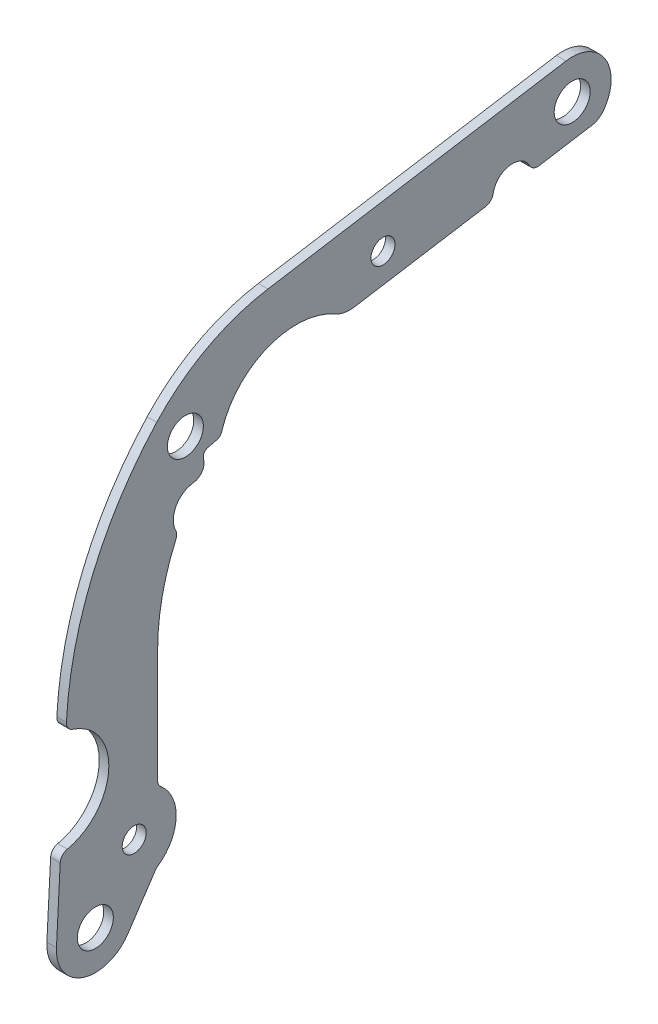
SolidWorks part; units mm, degrees
ref_plane "Front Plane" through (0, 0, 0) normal (0, 0, 1) x (1, 0, 0)
ref_plane "Top Plane" through (0, 0, 0) normal (0, 1, 0) x (1, 0, 0)
ref_plane "Right Plane" through (0, 0, 0) normal (1, 0, 0) x (0, 0, -1)
sketch "Sketch4" plane through (0, 0, 0) normal (1, 0, 0) x (0, 0, -1)
  line L1 (48.6487, 138.1253) -> (75.575, 142.4975) construction
  line L3 (57.5617, 155.7821) -> (157.0154, 171.931)
  line L4 (86.5165, 136.1694) -> (165.6977, 149.0264)
  line L5 (-12.9822, 0.6804) -> (-11.7283, 24.6061)
  line L6 (20.7807, 30.6129) -> (20.7807, 69.93)
  line L7 (20.7807, 30.6129) -> (20.3705, 7.1165) construction
  line L8 (10.8159, -7.2122) -> (20.3705, 7.1165)
  line L9 (0, 0) -> (159.099, 159.099) construction
  line L10 (0, 0) -> (0, 169.8564) construction
  line L11 (-10.2334, 53.1304) -> (-8.2428, 91.114) construction
  line L12 (20.4622, 135.7972) -> (39.6003, 118.1979) construction
  arc A0 (79.9562, 137.3555) -> (42.3764, 122.9235) centre (67.0666, 114.7754) ccw
  arc A1 (20.7807, 69.93) -> (39.6003, 118.1979) centre (92.0885, 69.93) cw
  arc A2 (79.9562, 137.3555) -> (86.5165, 136.1694) centre (84.9138, 146.0401) ccw
  arc A3 (-9.6558, 64.152) -> (20.4622, 135.7972) centre (104.9002, 58.1483) cw
  arc A4 (10.8159, -7.2122) -> (-12.9822, 0.6804) centre (0, 0) cw
  arc A5 (42.3764, 122.9235) -> (39.6003, 118.1979) centre (30.0312, 126.9975) cw
  arc A6 (165.6977, 149.0264) -> (169.5678, 151.3916) centre (164.7361, 154.9489) ccw
  arc A7 (169.5678, 151.3916) -> (157.0154, 171.931) centre (159.099, 159.099) ccw
  circle A8 centre (0, 0) radius 13 construction
  arc A9 (-9.3569, 27.3834) -> (-7.5877, 61.142) centre (-13, 44.5) ccw
  circle A10 centre (-13, 44.5) radius 17.5 construction
  circle A11 centre (30.0312, 126.9975) radius 13 construction
  arc A12 (20.3705, 7.1165) -> (20.7807, 30.6129) centre (12.9651, 18.9975) ccw
  arc A13 (-7.5877, 61.142) -> (-9.6558, 64.152) centre (-6.6599, 63.9949) cw
  circle A14 centre (159.099, 159.099) radius 13 construction
  circle A16 centre (-13, 44.5) radius 16.5 construction
  arc A17 (-9.3569, 27.3834) -> (-11.7283, 24.6061) centre (-8.7324, 24.4491) ccw
  arc A18 (57.5617, 155.7821) -> (20.4622, 135.7972) centre (67.8884, 92.1843) ccw
  point P35 (167.7007, 149.3517)
  dimension "D1" = 26
  dimension "D2" = 26
  dimension "D3" = 26
  dimension "D5" = 33
  dimension "D7" = 52
  dimension "D10" = 10
  dimension "D14" = 3
  dimension "D15" = 3
  dimension "D16" = 23
  dimension "D17" = 133
  dimension "D18" = 225
  dimension "D8" = 45
  dimension "D11" = 0
  dimension "D19" = 1
  dimension "D22" = 14
  dimension "D23" = 23.5
  dimension "D24" = 24
  dimension "D25" = 6
  dimension "D4" = 44.5
  dimension "D6" = 13
  dimension "D9" = 8
  dimension "D12" = 130.5
  dimension "D20" = 108
  dimension "D21" = 3
  dimension "D13" = 1
extrude "Extrude1" add sketch "Sketch4" along normal blind 3.2
sketch "Sketch5" plane through (0, 0, 0) normal (1, 0, 0) x (0, 0, -1)
  circle A0 centre (0, 0) radius 6
  circle A1 centre (159.099, 159.099) radius 6
  circle A2 centre (30.0312, 126.9975) radius 6
  circle A3 centre (30.0312, 126.9975) radius 13 construction
  dimension "D1" = 12
extrude "chassis mount holes" cut sketch "Sketch5" along normal through all
sketch "Sketch6" plane through (0, 0, 0) normal (1, 0, 0) x (0, 0, -1)
  line L0 (62.3633, 139.161) -> (111.358, 151.3468) construction
  line L2 (30.0312, 126.9975) -> (159.099, 159.099) construction
  circle A0 centre (12.9651, 18.9975) radius 4
  arc A1 (20.3705, 7.1165) -> (20.7807, 30.6129) centre (12.9651, 18.9975) ccw construction
  circle A2 centre (95.9755, 147.5209) radius 4
  dimension "D1" = 8
  dimension "D2" = 153
  dimension "D3" = 4
  dimension "D4" = 69.0642
  dimension "D5" = 63.1235
extrude "engine mount holes" cut sketch "Sketch6" along normal through all
sketch "Sketch7" plane through (0, 0, 0) normal (1, 0, 0) x (0, 0, -1)
  line L0 (86.5165, 136.1694) -> (165.6977, 149.0264) construction
  line L1 (159.099, 159.099) -> (160.8621, 148.2412) construction
  line L2 (30.0312, 126.9975) -> (0, 0) construction
  line L3 (38.0052, 118.03) -> (45.35, 119.8199) construction
  line L4 (38.0052, 118.03) -> (38.6616, 115.3364) construction
  line L5 (35.5885, 119.4997) -> (44.8764, 121.763)
  line L6 (35.5885, 119.4997) -> (36.7185, 114.8629)
  line L7 (36.7185, 114.8629) -> (44.8764, 121.763)
  circle A0 centre (139.1465, 144.7152) radius 6.5
  arc A1 (39.6003, 118.1979) -> (20.7807, 69.93) centre (92.0885, 69.93) ccw construction
  circle A2 centre (33.5173, 104.7692) radius 7.5
  circle A3 centre (30.0312, 126.9975) radius 6 construction
  dimension "D1" = 13
  dimension "D3" = 15
  dimension "D4" = 22.5
  dimension "D5" = 110
  dimension "D2" = 22
  dimension "D6" = 117
  dimension "D7" = 12
  dimension "D8" = 2
extrude "boss clearance" cut sketch "Sketch7" along normal through all
fillet "Fillet1" radius 3 5 edges at (1.6, 7.1165, -20.3705) (1.6, 30.6129, -20.7807) (1.6, 100.2369, -27.5416) (1.6, 145.757, -145.5624) (1.6, 143.6734, -132.7305)
fillet "Fillet2" radius 2 2 edges at (1.6, 119.4997, -35.5885) (1.6, 120.9497, -41.5388)
fillet "Fillet4" radius 4 4 edges at (0, 113.5355, -35.6672) (3.2, 113.5355, -35.6672) (1.6, 112.1836, -34.6477) (1.6, 114.8629, -36.7185)
